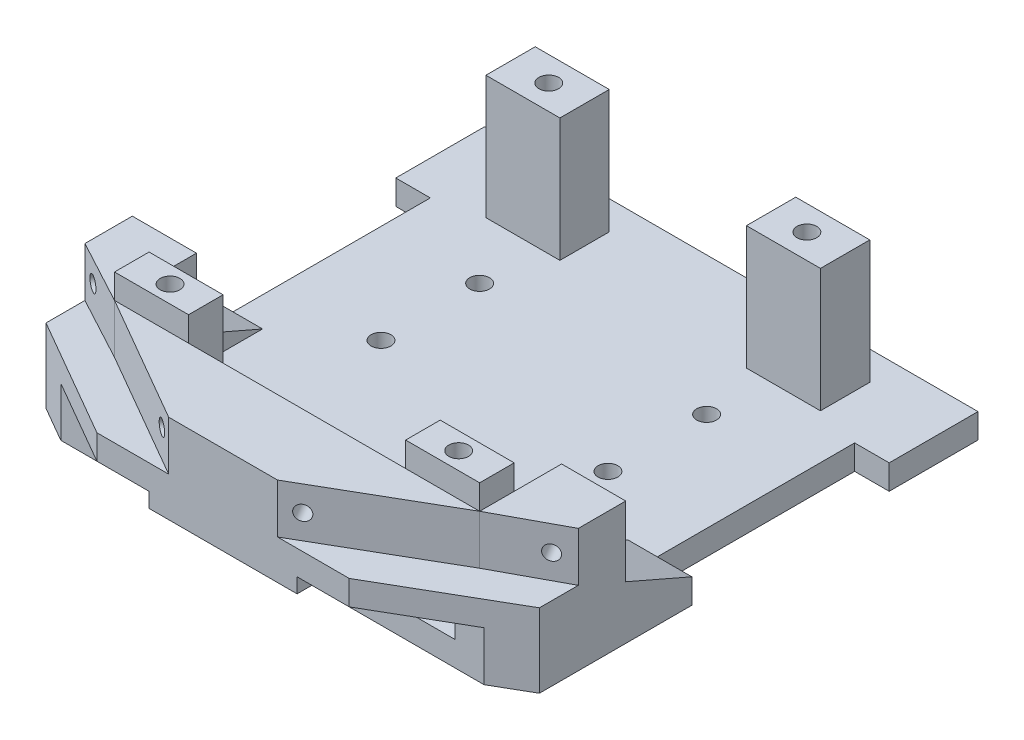
SolidWorks part; units mm, degrees
ref_plane "Front Plane" through (0, 0, 0) normal (0, 0, 1) x (1, 0, 0)
ref_plane "Top Plane" through (0, 0, 0) normal (0, 1, 0) x (1, 0, 0)
ref_plane "Right Plane" through (0, 0, 0) normal (1, 0, 0) x (0, 0, -1)
sketch "Sketch1" plane through (0, 0, 0) normal (0, 1, 0) x (1, 0, 0)
  line L0 (0, 107.1667) -> (0, 40) construction
  line L1 (-50, 40) -> (50, 40)
  line L2 (-50, 40) -> (-50, 22)
  line L3 (-50, -53) -> (-35, -53)
  line L4 (50, 40) -> (50, 22)
  line L5 (-83.0051, 2) -> (67.1687, 2) construction
  line L6 (-35, -53) -> (35, -53)
  line L7 (-50, 22) -> (-43, 22)
  line L9 (-50, -18) -> (-43, -18)
  line L10 (-43, 22) -> (-43, -18)
  line L11 (50, -18) -> (43, -18)
  line L12 (50, 22) -> (43, 22)
  line L19 (-50, -18) -> (-50, -53)
  line L22 (43, 22) -> (43, -18)
  line L23 (0, -68.8771) -> (0, -118.8333) construction
  line L24 (35, -53) -> (50, -53)
  line L25 (50, -18) -> (50, -53)
  circle A0 centre (-23, 12) radius 2
  circle A1 centre (-23, -8) radius 2
  circle A2 centre (23, -8) radius 2
  circle A3 centre (23, 12) radius 2
  point P0 (0, 0)
  point P9 (-43, 2)
  dimension "D11" = 4
  dimension "D12" = 18
  dimension "D10" = 10
  dimension "D1" = 100
  dimension "D2" = 40
  dimension "D3" = 43
  dimension "D4" = 40
  dimension "D5" = 35
  dimension "D6" = 15
  dimension "D13" = 20
  dimension "D15" = 20
extrude "Boss-Extrude1" add sketch "Sketch1" along normal blind 5
sketch "Sketch3" plane through (0, 5, 0) normal (0, 1, 0) x (1, 0, 0)
  line L0 (-37, -48) -> (-22, -48)
  line L1 (-33.9019, 34.1655) -> (-18.9019, 34.1655)
  line L2 (-33.9019, 34.1655) -> (-33.9019, 24.1655)
  line L3 (-33.9019, 24.1655) -> (-18.9019, 24.1655)
  line L4 (-18.9019, 34.1655) -> (-18.9019, 24.1655)
  line L5 (-22, -48) -> (-22, -41)
  line L6 (-22, -41) -> (-37, -41)
  line L7 (-37, -41) -> (-37, -48)
  line L8 (0, 59.3327) -> (0, -80.2758) construction
  line L9 (22, -41) -> (37, -41)
  line L10 (22, -48) -> (22, -41)
  line L11 (37, -48) -> (22, -48)
  line L12 (37, -41) -> (37, -48)
  line L13 (33.9019, 24.1655) -> (18.9019, 24.1655)
  line L14 (18.9019, 34.1655) -> (18.9019, 24.1655)
  line L15 (33.9019, 34.1655) -> (18.9019, 34.1655)
  line L16 (33.9019, 34.1655) -> (33.9019, 24.1655)
  line L18 (-50, -53) -> (50, -53) construction
  dimension "D1" = 15
  dimension "D2" = 10
  dimension "D3" = 7
  dimension "D4" = 15
  dimension "D5" = 13
  dimension "D6" = 5
extrude "Boss-Extrude3" add sketch "Sketch3" along normal blind 25
sketch "Sketch4" plane through (0, 30, 0) normal (0, 1, 0) x (1, 0, 0)
  line L0 (-22, -41) -> (-37, -41) construction
  line L1 (-22, -48) -> (-22, -41) construction
  line L2 (0, 50.6256) -> (0, -81.1778) construction
  line L3 (-33.9019, 24.1655) -> (-18.9019, 24.1655) construction
  line L4 (-18.9019, 24.1655) -> (-18.9019, 34.1655) construction
  circle A0 centre (-29.25, -44.5) radius 2
  circle A1 centre (29.25, -44.5) radius 2
  circle A2 centre (-26.1519, 29.1655) radius 2
  circle A3 centre (26.1519, 29.1655) radius 2
  dimension "D1" = 4
  dimension "D5" = 7.25
  dimension "D2" = 3.5
  dimension "D3" = 7.25
  dimension "D4" = 5
extrude "Cut-Extrude1" cut sketch "Sketch4" against normal blind 6
sketch "Sketch8" plane through (-37, 0, 0) normal (-1, 0, 0) x (0, 0, 1)
  line L1 (63, 15) -> (18, 15)
  line L2 (63, 15) -> (63, 5)
  line L3 (63, 5) -> (18, 5)
  line L4 (18, 15) -> (18, 5)
  line L5 (18, 5) -> (18, 0) construction
  line L6 (18, 5) -> (53, 5) construction
  dimension "D1" = 45
  dimension "D2" = 10
  dimension "D3" = 0
extrude "Boss-Extrude7" add sketch "Sketch8" along normal blind 13
mirror "Mirror2" about plane through (0, 0, 0) normal (1, 0, 0) of bodies 109
sketch "Sketch17" plane through (0, 15, 0) normal (0, 1, 0) x (1, 0, 0)
  line L0 (-50, -63) -> (-50, -18) construction
  line L1 (50, -63) -> (-50, -63)
  line L2 (50, -63) -> (50, -48)
  line L3 (50, -48) -> (-50, -48)
  line L4 (-50, -63) -> (-50, -48)
  dimension "D1" = 15
extrude "Boss-Extrude11" add sketch "Sketch17" against normal blind 5
sketch "Sketch18" plane through (0, 15, 0) normal (0, 1, 0) x (1, 0, 0)
  line L0 (-37, -48) -> (-11.0289, -63)
  line L2 (-50, -63) -> (50, -63) construction
  line L3 (0, -2.405) -> (0, -48) construction
  line L4 (-11.0289, -63) -> (11.0289, -63)
  line L5 (11.0289, -63) -> (37, -48)
  line L6 (22, -48) -> (-22, -48) construction
  line L7 (37, -48) -> (-37, -48)
  line L8 (0, -63) -> (0, -94.6894) construction
extrude "Boss-Extrude12" add sketch "Sketch18" along normal blind 10
sketch "Sketch19" plane through (0, 0, 63) normal (0, 0, 1) x (1, 0, 0)
  line L1 (-37, 10) -> (-37, 5)
  line L2 (-37, 5) -> (-50, 5)
  line L4 (-37, 10) -> (-50, 10)
  line L5 (-50, 5) -> (-50, 15) construction
  line L6 (-50, 10) -> (-50, 5)
  line L7 (0, 45.7661) -> (0, -17.7058) construction
  line L8 (37, 10) -> (50, 10)
  line L9 (37, 10) -> (37, 5)
  line L10 (37, 5) -> (50, 5)
  line L11 (50, 10) -> (50, 5)
extrude "Cut-Extrude7" cut sketch "Sketch19" against normal blind 10
sketch "Sketch20" plane through (0, 15, 0) normal (0, 1, 0) x (1, 0, 0)
  line L0 (-25.568, -63) -> (-50, -48.889)
  line L1 (-50, -63) -> (-11.0289, -63) construction
  line L2 (-50, -63) -> (-50, -18) construction
  line L3 (-37, -48) -> (-11.0289, -63) construction
  line L4 (-50, -48.889) -> (-50, -63)
  line L5 (-50, -63) -> (-25.568, -63)
  line L6 (0, -5.0362) -> (0, -79.6718) construction
  line L7 (50, -48.889) -> (50, -63)
  line L8 (25.568, -63) -> (50, -48.889)
  line L9 (50, -63) -> (25.568, -63)
extrude "Cut-Extrude8" cut sketch "Sketch20" against normal blind 20
sketch "Sketch21" plane through (50, 0, 0) normal (1, 0, 0) x (0, 0, -1)
  line L0 (-41, 15) -> (-18, 5)
  line L1 (-18, 5) -> (-18, 15)
  line L2 (-18, 15) -> (-18, 0) construction
  line L3 (-48.889, 15) -> (-18, 15) construction
  line L4 (-18, 15) -> (-41, 15)
extrude "Cut-Extrude9" cut sketch "Sketch21" against normal blind 120
sketch "Sketch23" plane through (0, 25, 0) normal (0, 1, 0) x (1, 0, 0)
  line L0 (-37, -48) -> (-50, -41)
  line L1 (-50, -41) -> (-50, -31.3942)
  line L2 (-50, -41) -> (-50, -18) construction
  line L3 (-50, -31.3942) -> (-37, -31.3942)
  line L4 (-37, -18) -> (-37, -41) construction
  line L5 (-37, -31.3942) -> (-37, -48)
  line L6 (0, -5.9698) -> (0, -45.471) construction
  line L7 (50, -31.3942) -> (37, -31.3942)
  line L8 (50, -41) -> (50, -31.3942)
  line L9 (37, -48) -> (50, -41)
  line L10 (37, -31.3942) -> (37, -48)
extrude "Boss-Extrude13" add sketch "Sketch23" against normal blind 20
sketch "Sketch22" plane through (-30.0436, 0, 52.0178) normal (-0.5001, 0, 0.8659) x (0.8659, 0, 0.5001)
  line L2 (21.9584, 25) -> (21.9584, 15) construction
  circle A0 centre (-18.7916, 20.6709) radius 1.5
  circle A1 centre (18.2084, 20.6709) radius 1.5
  dimension "D1" = 3
  dimension "D2" = 3.75
  dimension "D4" = 37
extrude "Cut-Extrude10" cut sketch "Sketch22" against normal blind 10 and the other way blind 10
sketch "Sketch24" plane through (30.0436, 0, 52.0178) normal (0.5001, 0, 0.8659) x (0.8659, 0, -0.5001)
  line L0 (-21.9584, 25) -> (-21.9584, 15) construction
  circle A0 centre (-18.2084, 19.9241) radius 1.5
  circle A1 centre (18.7916, 19.9241) radius 1.5
  dimension "D1" = 3
  dimension "D2" = 3.75
  dimension "D4" = 37
extrude "Cut-Extrude11" cut sketch "Sketch24" against normal blind 10 and the other way blind 10
sketch "Sketch25" plane through (0, 10, 0) normal (0, -1, 0) x (1, 0, 0)
  line L0 (-25.568, 63) -> (25.568, 63) construction
  line L1 (-15, 63) -> (15, 63)
  line L2 (-15, 63) -> (-15, 53)
  line L3 (-15, 53) -> (15, 53)
  line L4 (15, 63) -> (15, 53)
  point P6 (0, 53)
  dimension "D1" = 10
  dimension "D2" = 30
extrude "Boss-Extrude14" add sketch "Sketch25" along normal blind 3
